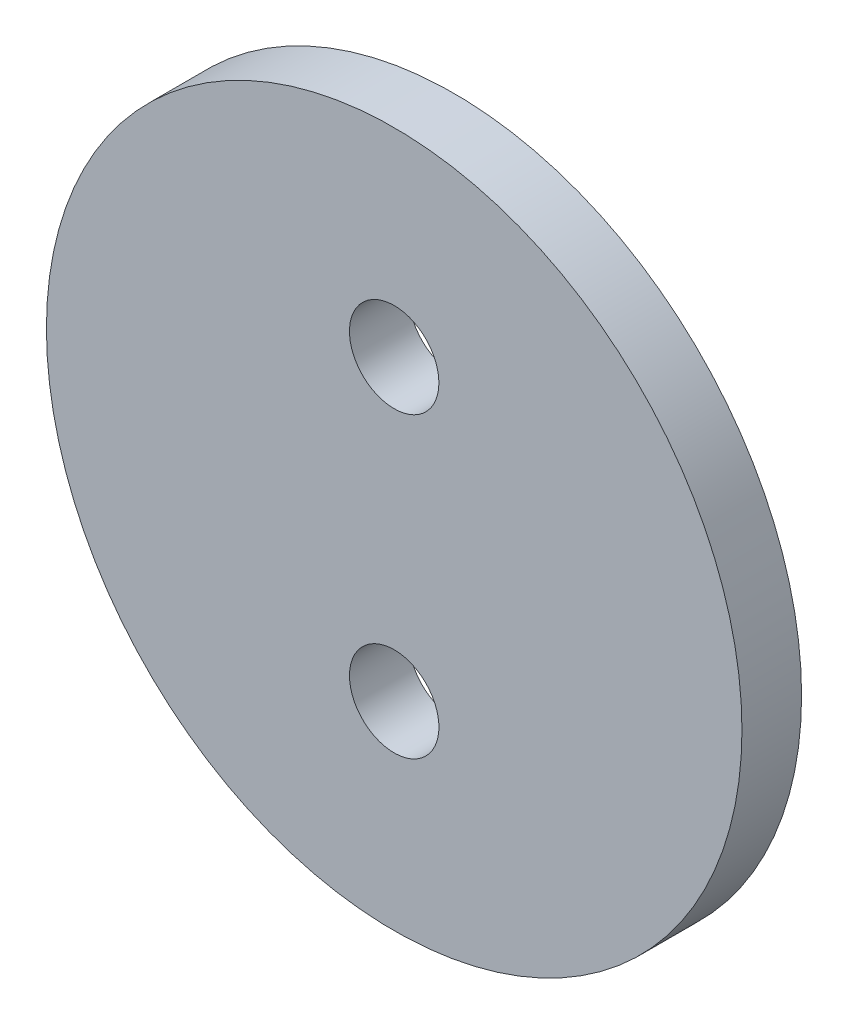
SolidWorks part; units mm, degrees
ref_plane "前视基准面" through (0, 0, 0) normal (0, 0, 1) x (1, 0, 0)
ref_plane "上视基准面" through (0, 0, 0) normal (0, 1, 0) x (1, 0, 0)
ref_plane "右视基准面" through (0, 0, 0) normal (1, 0, 0) x (0, 0, -1)
sketch "草图1" plane through (0, 0, 0) normal (0, 0, 1) x (1, 0, 0)
  circle A0 centre (0, 0) radius 7
extrude "凸台-拉伸1" add sketch "草图1" along normal blind 1.2
sketch "草图2" plane through (0, 0, 1.2) normal (0, 0, 1) x (1, 0, 0)
  line L0 (0, 0) -> (15.5284, 0) construction
  line L1 (0, 0) -> (0, 9.4324) construction
  circle A0 centre (0, 3) radius 0.9
  circle A1 centre (0, -3) radius 0.9
  dimension "D1" = 1.8
  dimension "D2" = 3
extrude "切除-拉伸1" cut sketch "草图2" against normal through all
